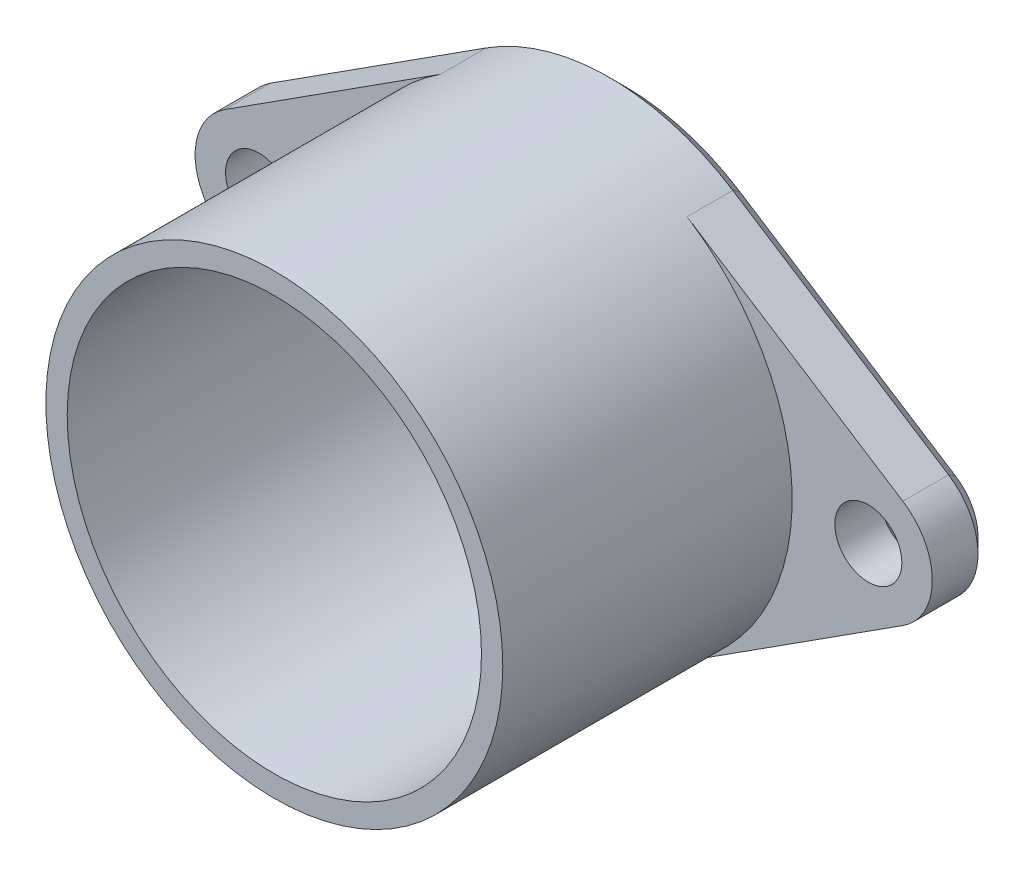
SolidWorks part; units mm, degrees
material "ABS"
ref_plane "Front" through (0, 0, 0) normal (0, 0, 1) x (1, 0, 0)
ref_plane "Top" through (0, 0, 0) normal (0, 1, 0) x (1, 0, 0)
ref_plane "Right" through (0, 0, 0) normal (1, 0, 0) x (0, 0, -1)
sketch "Эскиз2" plane through (0, 0, 0) normal (0, 0, 1) x (1, 0, 0)
  line L0 (4.05, 6.3125) -> (11.134, 1.7675)
  line L1 (11.134, -1.7675) -> (4.05, -6.3125)
  line L2 (-10, 0) -> (10, 0) construction
  line L3 (-4.05, -6.3125) -> (-11.134, -1.7675)
  line L4 (-4.05, 6.3125) -> (-11.134, 1.7675)
  line L5 (0, -7.5) -> (0, 7.5) construction
  arc A1 (11.134, 1.7675) -> (11.134, -1.7675) centre (10, 0) cw
  circle A2 centre (10, 0) radius 1.1
  arc A3 (4.05, -6.3125) -> (-4.05, -6.3125) centre (0, 0) cw
  circle A4 centre (-10, 0) radius 1.1
  arc A5 (-11.134, -1.7675) -> (-11.134, 1.7675) centre (-10, 0) cw
  arc A6 (4.05, 6.3125) -> (-4.05, 6.3125) centre (0, 0) ccw
  circle A7 centre (0, 4.5) radius 1
  circle A9 centre (0, -4.5) radius 1
  circle A10 centre (0, 0) radius 1.7
  point P12 (0, 0)
  dimension "D1" = 2.2
  dimension "D2" = 2.1
  dimension "D4" = 15
  dimension "D5" = 2
  dimension "D7" = 3.4
  dimension "D3" = 20
  dimension "D6" = 9
extrude "Бобышка-Вытянуть1" add sketch "Эскиз2" along normal blind 2
sketch "Эскиз3" plane through (0, 0, 2) normal (0, 0, 1) x (1, 0, 0)
  circle A0 centre (0, 0) radius 7.5
  arc A1 (-4.05, -6.3125) -> (4.05, -6.3125) centre (0, 0) ccw construction
extrude "Вытянуть-Тонкостенный1" add sketch "Эскиз3" along normal offset from surface (9.5 mm away) 11.5 thin up to face at (0, 0, 0) thin type one direction reverse wall 0.7
sketch "Эскиз4" plane through (0, 0, 2) normal (0, 0, 1) x (1, 0, 0)
  circle A0 centre (0, 0) radius 6.8
  circle A1 centre (0, 0) radius 6.8 construction
extrude "Вырез-Вытянуть1" cut sketch "Эскиз4" against normal blind 0.5
sketch "Эскиз5" plane through (0, 0, 1.5) normal (0, 0, 1) x (1, 0, 0)
  circle A0 centre (0, 0) radius 2.25
  dimension "D1" = 4.5
extrude "Вырез-Вытянуть2" cut sketch "Эскиз5" against normal blind 0.9
chamfer "Фаска1" distance 0.5 angle 45 13 edges at (-8.9, 0, 0) (1.7, 0, 0) (-1, -4.5, 0) (1, 4.5, 0) (11.1, 0, 0) (-7.592, 4.04, 0) (-12.1, 0, 0) (-7.592, -4.04, 0) (0, -7.5, 0) (7.592, -4.04, 0) (12.1, 0, 0) (7.592, 4.04, 0) (0, 7.5, 0)
